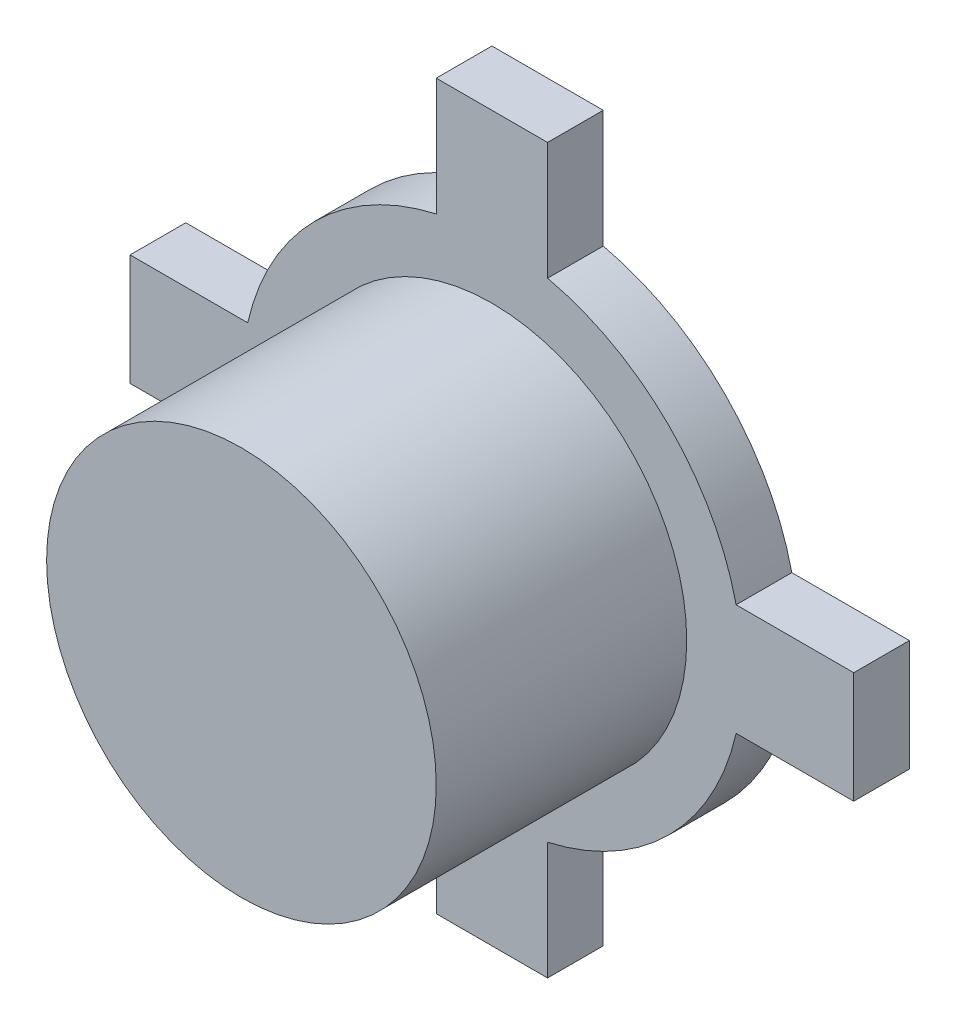
SolidWorks part; units mm, degrees
ref_plane "Front Plane" through (0, 0, 0) normal (0, 0, 1) x (1, 0, 0)
ref_plane "Top Plane" through (0, 0, 0) normal (0, 1, 0) x (1, 0, 0)
ref_plane "Right Plane" through (0, 0, 0) normal (1, 0, 0) x (0, 0, -1)
sketch "Sketch1" plane through (0, 0, 0) normal (0, 0, 1) x (1, 0, 0)
  circle A0 centre (0, 0) radius 3.5
  circle A1 centre (0, 0) radius 4 construction
  dimension "D1" = 0.5
extrude "Boss-Extrude1" add sketch "Sketch1" along normal blind 4.5
sketch "Sketch2" plane through (0, 0, 0) normal (0, 0, -1) x (-1, 0, 0)
  line L118 (-1, 6.5) -> (-1, 4.3875)
  line L119 (-4.3875, 1) -> (-6.5, 1)
  line L120 (-6.5, 1) -> (-6.5, -1)
  line L121 (-6.5, -1) -> (-4.3875, -1)
  line L122 (-1, -4.3875) -> (-1, -6.5)
  line L123 (-1, -6.5) -> (1, -6.5)
  line L124 (1, -6.5) -> (1, -4.3875)
  line L125 (4.3875, -1) -> (6.5, -1)
  line L126 (6.5, -1) -> (6.5, 1)
  line L127 (6.5, 1) -> (4.3875, 1)
  line L128 (1, 4.3875) -> (1, 6.5)
  line L129 (1, 6.5) -> (-1, 6.5)
  line L130 (-1, 6.5) -> (-1, 4.3875)
  line L131 (-4.3875, 1) -> (-6.5, 1)
  line L132 (-6.5, 1) -> (-6.5, -1)
  line L133 (-6.5, -1) -> (-4.3875, -1)
  line L134 (-1, -4.3875) -> (-1, -6.5)
  line L135 (-1, -6.5) -> (1, -6.5)
  line L136 (1, -6.5) -> (1, -4.3875)
  line L137 (4.3875, -1) -> (6.5, -1)
  line L138 (6.5, -1) -> (6.5, 1)
  line L139 (6.5, 1) -> (4.3875, 1)
  line L140 (1, 4.3875) -> (1, 6.5)
  line L141 (1, 6.5) -> (-1, 6.5)
  arc A37 (-1, 4.3875) -> (-4.3875, 1) centre (0, 0) ccw
  arc A38 (-4.3875, -1) -> (-1, -4.3875) centre (0, 0) ccw
  arc A39 (1, -4.3875) -> (4.3875, -1) centre (0, 0) ccw
  arc A40 (4.3875, 1) -> (1, 4.3875) centre (0, 0) ccw
  arc A41 (-1, 4.3875) -> (-4.3875, 1) centre (0, 0) ccw
  arc A42 (-4.3875, -1) -> (-1, -4.3875) centre (0, 0) ccw
  arc A43 (1, -4.3875) -> (4.3875, -1) centre (0, 0) ccw
  arc A44 (4.3875, 1) -> (1, 4.3875) centre (0, 0) ccw
  dimension "D1" = 0.5
extrude "Boss-Extrude2" add sketch "Sketch2" along normal blind 1
